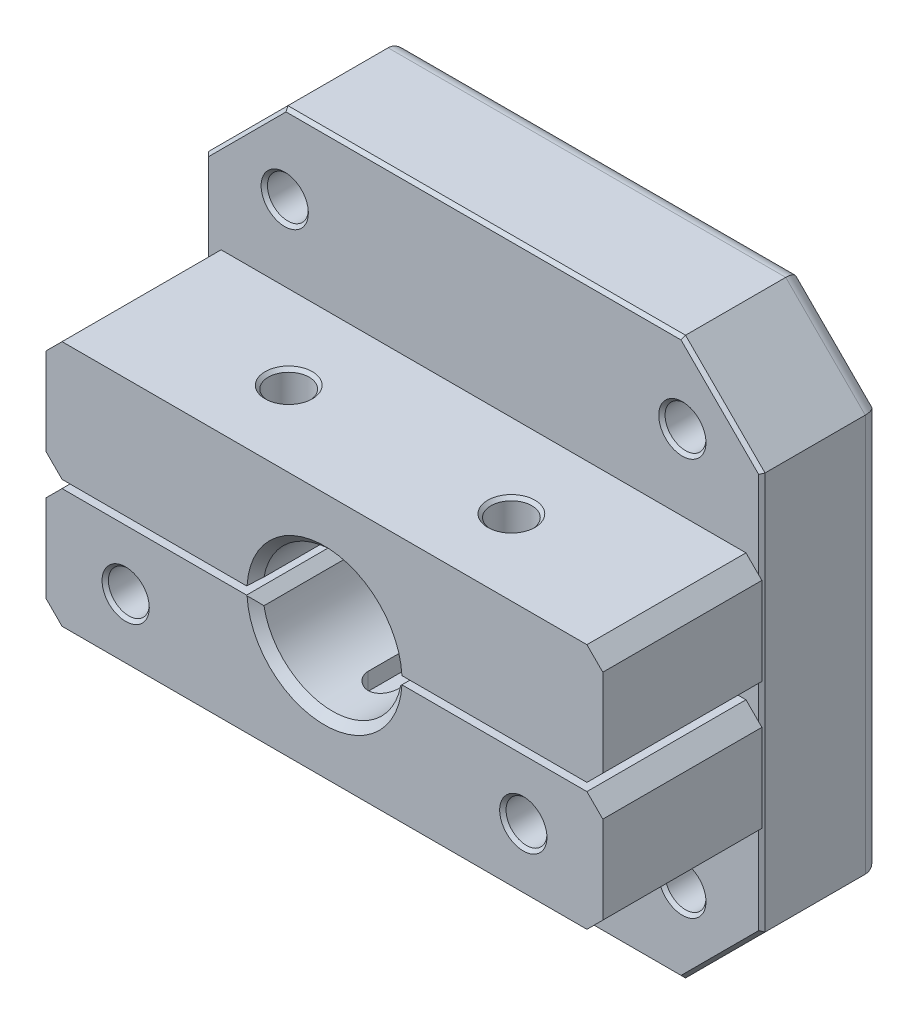
SolidWorks part; units mm, degrees
note: The reader was unsure of these and kept them because the rebuilt part matched: shared geometry of "Sketch1<3>", "Sketch1<6>", "Sketch1<7>", "Sketch1<4>", "Sketch1<5>".
material "AISI 1020"
ref_plane "Front Plane" through (0, 0, 0) normal (0, 0, 1) x (1, 0, 0)
ref_plane "Top Plane" through (0, 0, 0) normal (0, 1, 0) x (1, 0, 0)
ref_plane "Right Plane" through (0, 0, 0) normal (1, 0, 0) x (0, 0, -1)
sketch "Sketch1" plane through (0, 0, 0) normal (0, 0, 1) x (1, 0, 0)
  line L0 (0, 44.45) -> (0, -44.45) construction
  line L1 (-44.45, 44.45) -> (44.45, 44.45)
  line L2 (-44.45, 44.45) -> (-44.45, -44.45)
  line L3 (-44.45, -44.45) -> (44.45, -44.45)
  line L4 (44.45, 44.45) -> (44.45, -44.45)
  line L5 (-44.45, 0) -> (44.45, 0) construction
  line L6 (-44.45, 0) -> (-44.45, -0.635)
  line L7 (-44.45, -0.635) -> (0, -0.635) construction
  line L8 (0, -0.635) -> (-11.0943, -0.635) construction
  line L9 (-11.0943, -0.635) -> (-44.45, -0.635)
  line L10 (-44.45, -0.635) -> (-44.45, -19.685)
  line L11 (-44.45, -19.685) -> (44.45, -19.685)
  line L12 (11.0943, -0.635) -> (44.45, -0.635)
  line L13 (44.45, -0.635) -> (44.45, -19.685)
  line L14 (11.0943, 0.635) -> (44.45, 0.635)
  line L15 (44.45, 0.635) -> (44.45, 19.685)
  line L16 (-44.45, 19.685) -> (44.45, 19.685)
  line L17 (-44.45, 0.635) -> (-44.45, 19.685)
  line L18 (-11.0943, 0.635) -> (-44.45, 0.635)
  line L19 (-44.45, -10.16) -> (-31.75, -10.16) construction
  line L20 (-31.75, -10.16) -> (-31.75, -19.685) construction
  line L21 (0, -11.1125) -> (2.413, -11.1125)
  line L22 (2.413, -11.1125) -> (2.413, -13.6207)
  line L23 (2.413, -13.6207) -> (-2.413, -13.6207)
  line L24 (2.413, -11.1125) -> (2.413, -10.8474)
  line L25 (-2.413, -11.1125) -> (-2.413, -10.8474)
  line L26 (-2.413, -11.1125) -> (-2.413, -13.6207)
  circle A0 centre (0, 0) radius 11.1125
  circle A1 centre (31.75, 31.75) radius 3.2639
  circle A2 centre (-31.75, 31.75) radius 3.2639
  circle A3 centre (31.75, -31.75) radius 3.2639
  circle A4 centre (-31.75, -31.75) radius 3.2639
  circle A5 centre (-31.75, -10.16) radius 3.2639
  circle A6 centre (31.75, -10.16) radius 3.2639
  circle A7 centre (0, 0) radius 4.7625
  arc A8 (-2.413, -13.6207) -> (2.413, -13.6207) centre (0, -13.6207) ccw
  circle A9 centre (0, 0) radius 4.8133
  circle A10 centre (0, 0) radius 4.7625 construction
  point P28 (0, -19.685)
  point P51 (0, -13.6207)
  dimension "D5" = 6.5278
  dimension "D2" = 88.9
  dimension "D3" = 12.7
  dimension "D4" = 12.7
  dimension "D6" = 0.635
  dimension "D7" = 19.685
  dimension "D8" = 88.9
  dimension "D9" = 12.7
  dimension "D10" = 2.5082
  dimension "D11" = 2.413
  dimension "D12" = 0.0508
extrude "Boss-Extrude1" add sketch "Sketch1" along normal blind 9.525 contours L2 L16 L4 L1 A1 A2 | A0 L14 L4 L16 L2 L18 | A0 L9 L2 L11 L4 L12 A5 A6 | L11 L2 L3 L4 A4 A3 | A0 L18 L2 L9 | A0 L12 L4 L14 | A0 L25 L26 L23 L22 L21 | A0 L21 L24 | L23 A8
extrude "Boss-Extrude2" add sketch "Sketch1<3>" along normal blind 25.4 from surface at 9.525 separate body contours A0 L9 L10 L11 L13 L12 | A0 L25 L26 L23 L22 L21 | A0 L21 L24 | L23 A8
sketch "Sketch1<3>" plane through (0, 0, 0) normal (0, 0, 1) x (1, 0, 0) same geometry as "Sketch1"
extrude "Cut-Extrude2" cut sketch "Sketch1<6>" along normal blind 27.94 contours A0 L25 L26 L23 L22 L21 | A0 L21 L24
sketch "Sketch1<6>" plane through (0, 0, 0) normal (0, 0, 1) x (1, 0, 0) same geometry as "Sketch1"
extrude "Cut-Extrude3" cut sketch "Sketch1<7>" along normal up to vertex (9.525 mm away) contours L23 A8
sketch "Sketch1<7>" plane through (0, 0, 0) normal (0, 0, 1) x (1, 0, 0) same geometry as "Sketch1"
extrude "Boss-Extrude3" add sketch "Sketch1<4>" against normal blind 25.4 from surface at 34.925 separate body contours A0 L14 L15 L16 L17 L18 starting at face at (-28.4861, -10.16, 34.925)
sketch "Sketch1<4>" plane through (0, 0, 0) normal (0, 0, 1) x (1, 0, 0) same geometry as "Sketch1"
sketch "Sketch2" plane through (0, 0, 0) normal (0, 1, 0) x (1, 0, 0)
  line L0 (0, 0) -> (0, -9.525)
  line L1 (0, -9.525) -> (0, -10.795)
  line L2 (0, -22.86) -> (17.78, -22.86)
  line L3 (0, -10.795) -> (0, -34.925)
  circle A0 centre (17.78, -22.86) radius 3.2639
  circle A2 centre (0, -22.86) radius 1.7859
  circle A3 centre (-17.78, -22.86) radius 3.2639
  dimension "D1" = 9.525
  dimension "D3" = 6.5278
  dimension "D4" = 3.5719
  dimension "D2" = 1.27
  dimension "D6" = 17.78
extrude "Cut-Extrude1" cut sketch "Sketch2" against normal through all both and the other way through all
extrude "Boss-Extrude4" add sketch "Sketch1<5>" against normal blind 9.525 contours L11 L2 L3 L4 A4 A3 | A8 L26 L25 A0 L9 L2 L11 L4 L12 L24 L22 A5 A6 | L23 A8 | A0 L25 L26 L23 L22 L21 | A0 A7 | A0 L21 L24 | A0 L14 L4 L16 L2 L18 | L2 L16 L4 L1 A1 A2 | A0 L18 L2 L9 | A0 L12 L4 L14
sketch "Sketch1<5>" plane through (0, 0, 0) normal (0, 0, 1) x (1, 0, 0) same geometry as "Sketch1"
chamfer "Chamfer1" distance 12.7 angle 45 4 edges at (-44.45, -44.45, 0) (44.45, -44.45, 0) (44.45, 44.45, 0) (-44.45, 44.45, 0)
chamfer "Chamfer2" distance 2.54 angle 45 4 edges at (44.45, -0.635, 22.225) (-44.45, -0.635, 22.225) (-44.45, -19.685, 22.225) (44.45, -19.685, 22.225)
chamfer "Chamfer3" distance 2.54 angle 45 4 edges at (-44.45, 0.635, 22.225) (-44.45, 19.685, 22.225) (44.45, 19.685, 22.225) (44.45, 0.635, 22.225)
chamfer "Chamfer4" distance 1.27 angle 45 3 edges at (11.0943, -0.635, 22.225) (-11.0943, -0.635, 22.225) (0, -11.1125, 34.925)
chamfer "Chamfer5" distance 1.27 angle 45 4 edges at (-11.0943, 0.635, 22.225) (11.0943, 0.635, 22.225) (0, 11.1125, 9.525) (0, 11.1125, 34.925)
chamfer "Chamfer6" distance 0.508 angle 45 12 edges at (38.1, -38.1, 9.525) (44.45, 0, 9.525) (38.1, 38.1, 9.525) (0, 44.45, 9.525) (-38.1, 38.1, 9.525) (-44.45, 0, 9.525) (-38.1, -38.1, 9.525) (0, -44.45, 9.525) (35.0139, 31.75, 9.525) (-28.4861, 31.75, 9.525) (-28.4861, -31.75, 9.525) (35.0139, -31.75, 9.525)
chamfer "Chamfer7" distance 0.508 angle 45 4 edges at (14.5161, 0.635, 22.86) (-14.5161, 0.635, 22.86) (-21.0439, 19.685, 22.86) (14.5161, 19.685, 22.86)
chamfer "Chamfer8" distance 0.508 angle 45 6 edges at (21.0439, -0.635, 22.86) (-17.78, -0.635, 26.1239) (-14.5161, -19.685, 22.86) (21.0439, -19.685, 22.86) (-28.4861, -10.16, 34.925) (35.0139, -10.16, 34.925)
fillet "Fillet1" radius 2.413 2 edges at (2.413, -12.2341, 27.94) (-2.413, -12.2341, 27.94)
sketch "Sketch3" plane through (0, 0, 0) normal (0, 0, 1) x (1, 0, 0)
  circle A0 centre (0, 0) radius 11.1379
extrude "Cut-Extrude4" cut sketch "Sketch3" along normal up to surface (9.525 mm away) up to face at (35.5219, 31.75, 9.525)
fillet "Fillet2" radius 2.54 8 edges at (44.45, 0, -9.525) (38.1, 38.1, -9.525) (0, 44.45, -9.525) (-38.1, 38.1, -9.525) (-44.45, 0, -9.525) (-38.1, -38.1, -9.525) (0, -44.45, -9.525) (38.1, -38.1, -9.525)
split "Split1" bodies to split 107 108 106 120 resulting bodies 109 110 111
equation "\"Shaft Diameter\"= 7 / 8"
equation "\"Overall Width\"= 3.5"
equation "\"Overall Height\"= \"Bracket Plate Thickness\" + 1"
equation "\"Bolt Diameter Plate\"= .257"
equation "\"Bolt Diameter Bracket\"= .257"
equation "\"D3@Sketch1\"=\"Bolt from edge\""
equation "\"D2@Sketch1\"=\"Overall Width\""
equation "\"D1@Sketch1\"=\"Shaft Diameter\""
equation "\"Bolt from edge\"= .5"
equation "\"D4@Sketch1\"=\"Bolt from edge\""
equation "\"D5@Sketch1\"=\"Bolt Diameter Plate\""
equation "\"Bracket Gap\"= .05"
equation "\"Bracket Plate Thickness\"= 3 / 4"
equation "\"D6@Sketch1\"=\"Bracket Gap\"/2"
equation "\"D7@Sketch1\"=\"Bracket Plate Thickness\"+\"Bracket Gap\"/2"
equation "\"D1@Boss-Extrude1\"=\"Bracket Plate Thickness\"/2"
equation "\"D1@Boss-Extrude2\"=\"Overall Height\"-\"Bracket Plate Thickness\""
equation "\"D3@Sketch2\"=\"Bolt Diameter Bracket\""
equation "\"D1@Boss-Extrude3\"=\"Overall Height\"-\"Bracket Plate Thickness\""
equation "\"Pin bolt diameter\"= 9 / 64'#6 bolt"
equation "\"D4@Sketch2\"=\"Pin bolt diameter\""
equation "\"D9@Sketch1\"=\"Bolt from edge\""
equation "\"D1@Boss-Extrude4\"=\"Bracket Plate Thickness\"/2"
equation "\"D1@Sketch2\"=\"Bracket Plate Thickness\"/2"
equation "\"D2@Sketch2\"=\"Bracket Gap\""
equation "\"Keyway Width\"= 3 / 16 + .0025"
equation "\"Keyway Height\"= 3 / 16 + .01"
equation "\"D10@Sketch1\"=\"Keyway Height\"/2"
equation "\"D11@Sketch1\"=\"Keyway Width\"/2"
equation "\"D1@Fillet1\"=\"Keyway Width\"/2"
equation "\"D1@Sketch3\"=\"Shaft Diameter\"+.002"
